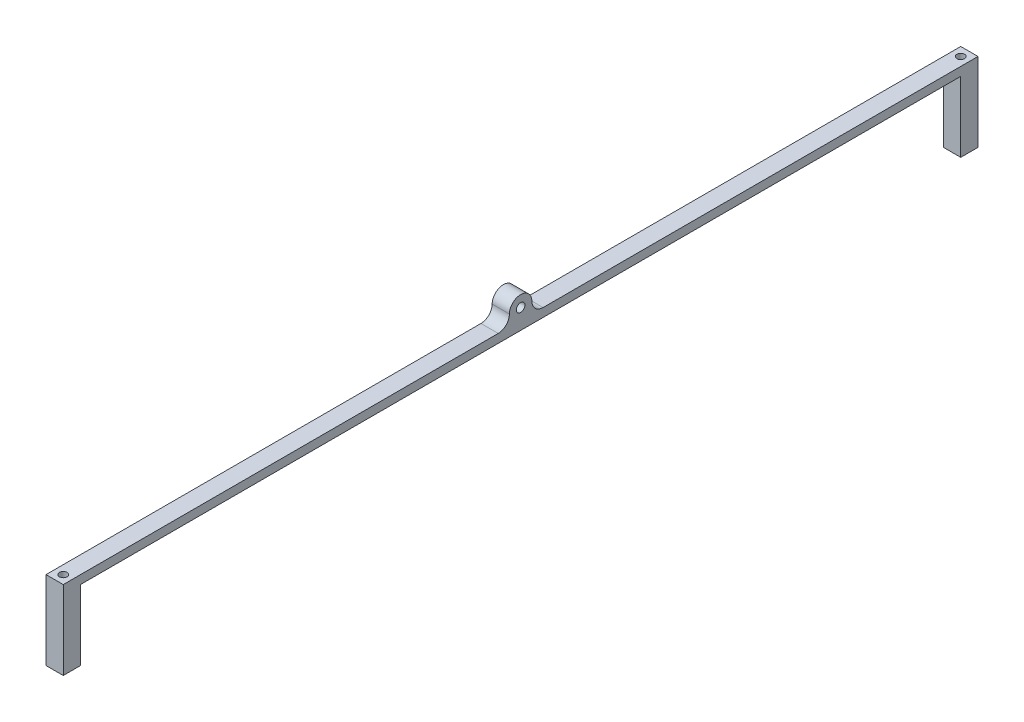
SolidWorks part; units mm, degrees
ref_plane "Спереди" through (0, 0, 0) normal (0, 0, 1) x (1, 0, 0)
ref_plane "Сверху" through (0, 0, 0) normal (0, 1, 0) x (1, 0, 0)
ref_plane "Справа" through (0, 0, 0) normal (1, 0, 0) x (0, 0, -1)
other "Configuration Table"
sketch "Эскиз1" plane through (0, 0, 0) normal (0, 1, 0) x (1, 0, 0)
  line L1 (0, 530) -> (10, 530)
  line L2 (0, 530) -> (0, 0)
  line L3 (0, 0) -> (10, 0)
  line L4 (10, 530) -> (10, 0)
  line L5 (592.3, 530) -> (592.3, 0) construction
  line L7 (0, 520) -> (10, 530) construction
  line L10 (0, 520) -> (10, 520) construction
  line L14 (0, 10) -> (10, 10) construction
  line L16 (0, 530) -> (10, 520) construction
  line L17 (0, 10) -> (10, 0) construction
  line L18 (10, 10) -> (0, 0) construction
  circle A0 centre (5, 525) radius 2.25
  circle A1 centre (5, 5) radius 2.25
  dimension "D5" = 4.5
  dimension "D6" = 4.5
  dimension "D2" = 10
  dimension "D3" = 10
  dimension "D4" = 10
extrude "Бобышка-Вытянуть1" add sketch "Эскиз1" along normal blind 5
sketch "Эскиз2" plane through (0, 0, 0) normal (1, 0, 0) x (0, 0, -1)
  line L0 (258.5, 11.5) -> (271.5, 11.5) construction
  line L1 (252, 5) -> (278, 5)
  line L2 (0, 5) -> (530, 5) construction
  arc A0 (271.5, 11.5) -> (258.5, 11.5) centre (265, 11.5) ccw
  arc A2 (252, 5) -> (258.5, 11.5) centre (252, 11.5) ccw
  arc A3 (271.5, 11.5) -> (278, 5) centre (278, 11.5) ccw
  circle A4 centre (265, 11.5) radius 2.5
  point P1 (265, 5)
  point P5 (265, 5)
  point P6 (271.5, 11.5)
  point P7 (258.5, 11.5)
  dimension "D1" = 13
  dimension "D2" = 13
  dimension "D3" = 13
  dimension "D4" = 5
extrude "Бобышка-Вытянуть2" add sketch "Эскиз2" along normal blind 10
sketch "Эскиз3" plane through (0, 0, 0) normal (0, -1, 0) x (1, 0, 0)
  line L0 (10, 0) -> (10, -530) construction
  line L1 (0, 0) -> (10, 0)
  line L2 (0, 0) -> (0, -10)
  line L3 (0, -10) -> (10, -10)
  line L4 (10, 0) -> (10, -10)
  line L6 (0, -530) -> (10, -530)
  line L7 (0, -530) -> (0, -520)
  line L8 (0, -520) -> (10, -520)
  line L9 (10, -530) -> (10, -520)
  circle A526 centre (5, -525) radius 2.25
  circle A527 centre (5, -525) radius 2.25
  circle A529 centre (5, -5) radius 2.25
  circle A530 centre (5, -5) radius 2.25
  dimension "D1" = 10
  dimension "D2" = 10
  dimension "D3" = 0
  dimension "D4" = 0
extrude "Бобышка-Вытянуть3" add sketch "Эскиз3" along normal up to surface (40.65 mm away)
